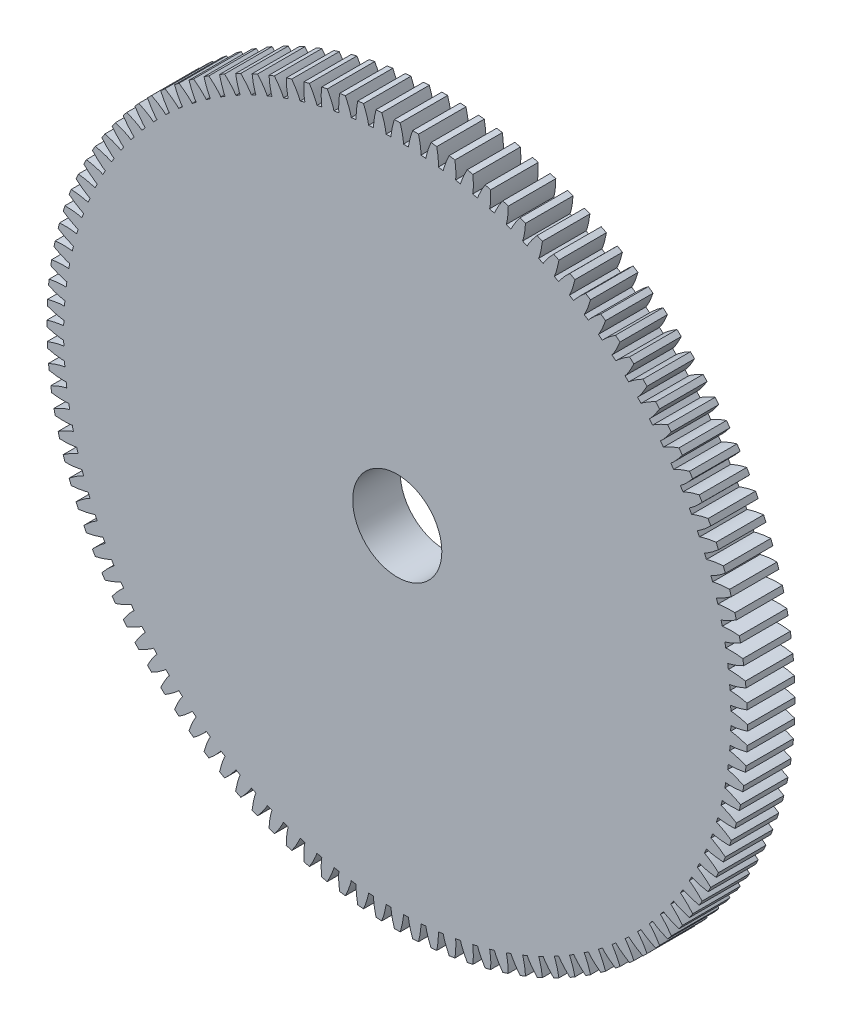
SolidWorks part; units mm, degrees
material "Brass"
ref_plane "Front Plane" through (0, 0, 0) normal (0, 0, 1) x (1, 0, 0)
ref_plane "Top Plane" through (0, 0, 0) normal (0, 1, 0) x (1, 0, 0)
ref_plane "Right Plane" through (0, 0, 0) normal (1, 0, 0) x (0, 0, -1)
sketch "Sketch1" plane through (0, 0, 0) normal (0, 0, 1) x (1, 0, 0)
  circle A0 centre (0, 0) radius 51.6467
extrude "Boss-Extrude1" add sketch "Sketch1" along normal blind 7
sketch "Sketch2" plane through (0, 0, 0) normal (0, 0, 1) x (1, 0, 0)
  circle A0 centre (0, 0) radius 6.5714
  dimension "D1" = 13.1428
extrude "Cut-Extrude2" cut sketch "Sketch2" against normal blind 9 and the other way blind 9
sketch "Sketch3" plane through (0, 0, 0) normal (0, 0, 1) x (1, 0, 0)
  spline S0 degree 4 poles (49.1734, 0.9164) (49.1838, 0.9166) (49.2037, 0.9164) (49.236, 0.9157) (49.2811, 0.9138) (49.3345, 0.9109) (49.3975, 0.9065) (49.4669, 0.9007) (49.5426, 0.8933) (49.6181, 0.8849) (49.6937, 0.8757) (49.769, 0.8656) (49.8604, 0.8525) (49.9703, 0.8355) (50.099, 0.8136) (50.2454, 0.7864) (50.3952, 0.7562) (50.5429, 0.7245) (50.6927, 0.69) (50.8381, 0.655) (50.9896, 0.6161) (51.1298, 0.579) (51.2875, 0.5348) (51.415, 0.4982) (51.584, 0.4471) (51.6841, 0.416) (51.8014, 0.3786) (51.8537, 0.3614) (51.8859, 0.3509) knots 0 0 0 0 0 0.015084 0.028532 0.04661 0.064855 0.092111 0.119476 0.146842 0.174209 0.201575 0.228941 0.256307 0.307035 0.361767 0.4165 0.471232 0.525964 0.580697 0.635429 0.690161 0.744894 0.799626 0.854358 0.909091 0.954545 1 1 1 1 1 construction
  spline S1 degree 4 poles (49.1734, 0.9164) (49.1838, 0.9166) (49.2037, 0.9164) (49.236, 0.9157) (49.2811, 0.9138) (49.3345, 0.9109) (49.3975, 0.9065) (49.4669, 0.9007) (49.5426, 0.8933) (49.6181, 0.8849) (49.6937, 0.8757) (49.769, 0.8656) (49.8604, 0.8525) (49.9703, 0.8355) (50.099, 0.8136) (50.2454, 0.7864) (50.3952, 0.7562) (50.5429, 0.7245) (50.6927, 0.69) (50.8381, 0.655) (50.9896, 0.6161) (51.1298, 0.579) (51.2875, 0.5348) (51.415, 0.4982) (51.5474, 0.4582) (51.6119, 0.4383) (51.6449, 0.428) knots 0 0 0 0 0 0.015084 0.028532 0.04661 0.064855 0.092111 0.119476 0.146842 0.174209 0.201575 0.228941 0.256307 0.307035 0.361767 0.4165 0.471232 0.525964 0.580697 0.635429 0.690161 0.744894 0.799626 0.854358 0.909091 0.909091 0.909091 0.909091 0.909091
  spline S2 degree 4 poles (49.1539, 1.6583) (49.1644, 1.6588) (49.1842, 1.66) (49.2165, 1.6624) (49.2614, 1.6666) (49.3146, 1.6723) (49.3773, 1.68) (49.4463, 1.6894) (49.5214, 1.7008) (49.5965, 1.7131) (49.6714, 1.7263) (49.7461, 1.7403) (49.8367, 1.7581) (49.9455, 1.7809) (50.0729, 1.8095) (50.2177, 1.8443) (50.3657, 1.8823) (50.5116, 1.9217) (50.6594, 1.964) (50.8027, 2.0066) (50.952, 2.0533) (51.09, 2.0977) (51.2452, 2.1502) (51.3706, 2.1933) (51.5367, 2.2532) (51.635, 2.2895) (51.7503, 2.333) (51.8016, 2.3529) (51.8332, 2.3651) knots 0 0 0 0 0 0.015084 0.028532 0.04661 0.064855 0.092111 0.119476 0.146842 0.174209 0.201575 0.228941 0.256307 0.307035 0.361767 0.4165 0.471232 0.525964 0.580697 0.635429 0.690161 0.744894 0.799626 0.854358 0.909091 0.954545 1 1 1 1 1 construction
  spline S3 degree 4 poles (49.1539, 1.6583) (49.1644, 1.6588) (49.1842, 1.66) (49.2165, 1.6624) (49.2614, 1.6666) (49.3146, 1.6723) (49.3773, 1.68) (49.4463, 1.6894) (49.5214, 1.7008) (49.5965, 1.7131) (49.6714, 1.7263) (49.7461, 1.7403) (49.8367, 1.7581) (49.9455, 1.7809) (50.0729, 1.8095) (50.2177, 1.8443) (50.3657, 1.8823) (50.5116, 1.9217) (50.6594, 1.964) (50.8027, 2.0066) (50.952, 2.0533) (51.09, 2.0977) (51.2452, 2.1502) (51.3706, 2.1933) (51.5007, 2.2403) (51.5641, 2.2634) (51.5965, 2.2754) knots 0 0 0 0 0 0.015084 0.028532 0.04661 0.064855 0.092111 0.119476 0.146842 0.174209 0.201575 0.228941 0.256307 0.307035 0.361767 0.4165 0.471232 0.525964 0.580697 0.635429 0.690161 0.744894 0.799626 0.854358 0.909091 0.909091 0.909091 0.909091 0.909091
  spline S4 degree 4 poles (49.152, 1.7331) (49.1521, 1.7275) (49.1524, 1.7162) (49.1528, 1.7032) (49.1537, 1.6661) (49.1542, 1.6496) (49.1554, 1.6026) (49.1561, 1.5744) (49.1572, 1.5339) (49.158, 1.5022) (49.1589, 1.4673) (49.1598, 1.4358) (49.1606, 1.4032) (49.1615, 1.3704) (49.1623, 1.3377) (49.1632, 1.3038) (49.1641, 1.2685) (49.1651, 1.2321) (49.1661, 1.1947) (49.1671, 1.1572) (49.168, 1.1226) (49.1689, 1.0853) (49.1698, 1.0523) (49.1709, 1.0096) (49.1717, 0.9804) (49.1731, 0.927) (49.1735, 0.9094) (49.1745, 0.8714) (49.1749, 0.857) (49.1752, 0.847) (49.1753, 0.8418) knots 0 0 0 0 0 0.022088 0.044177 0.083333 0.119319 0.159813 0.201093 0.243304 0.280291 0.314751 0.350761 0.388774 0.424594 0.463227 0.497138 0.541352 0.583276 0.626202 0.666552 0.706902 0.743676 0.7856 0.828955 0.87417 0.916667 0.958835 0.979418 1 1 1 1 1 construction
  spline S5 degree 4 poles (49.1539, 1.6583) (49.1541, 1.6517) (49.1545, 1.6378) (49.1554, 1.6026) (49.1561, 1.5744) (49.1572, 1.5339) (49.158, 1.5022) (49.1589, 1.4673) (49.1598, 1.4358) (49.1606, 1.4032) (49.1615, 1.3704) (49.1623, 1.3377) (49.1632, 1.3038) (49.1641, 1.2685) (49.1651, 1.2321) (49.1661, 1.1947) (49.1671, 1.1572) (49.168, 1.1226) (49.1689, 1.0853) (49.1698, 1.0523) (49.1709, 1.0096) (49.1717, 0.9804) (49.1727, 0.94) (49.1732, 0.9243) (49.1734, 0.9164) knots 0.083333 0.083333 0.083333 0.083333 0.083333 0.119319 0.159813 0.201093 0.243304 0.280291 0.314751 0.350761 0.388774 0.424594 0.463227 0.497138 0.541352 0.583276 0.626202 0.666552 0.706902 0.743676 0.7856 0.828955 0.87417 0.916667 0.916667 0.916667 0.916667 0.916667
  spline S6 degree 4 poles (50.8043, 0.4211) (50.864, 0.4216) (50.9794, 0.4225) (51.1316, 0.4238) (51.5629, 0.4274) (51.7496, 0.4289) (52.3065, 0.4335) (52.6262, 0.4362) (53.0785, 0.4399) (53.4484, 0.443) (53.8676, 0.4465) (54.2464, 0.4496) (54.6546, 0.453) (55.0383, 0.4562) (55.4322, 0.4594) (55.8223, 0.4627) (56.2055, 0.4658) (56.6028, 0.4691) (56.9958, 0.4724) (57.4001, 0.4757) (57.7912, 0.479) (58.2102, 0.4825) (58.5784, 0.4855) (59.0365, 0.4893) (59.3484, 0.4919) (59.8904, 0.4964) (60.0774, 0.4979) (60.499, 0.5014) (60.6501, 0.5027) (60.7751, 0.5037) (60.8382, 0.5042) knots 0 0 0 0 0 0.020582 0.041165 0.083333 0.123922 0.164487 0.203919 0.245641 0.283463 0.324863 0.363448 0.401438 0.443624 0.479586 0.519794 0.557378 0.596758 0.637386 0.678142 0.716036 0.757316 0.79719 0.837516 0.878097 0.916667 0.955572 0.977786 1 1 1 1 1 construction
  spline S7 degree 4 poles (51.6449, 0.428) (51.7297, 0.4287) (51.8939, 0.4301) (52.3065, 0.4335) (52.6262, 0.4362) (53.0785, 0.4399) (53.4484, 0.443) (53.8676, 0.4465) (54.2464, 0.4496) (54.6546, 0.453) (55.0383, 0.4562) (55.4322, 0.4594) (55.8223, 0.4627) (56.2055, 0.4658) (56.6028, 0.4691) (56.9958, 0.4724) (57.4001, 0.4757) (57.7912, 0.479) (58.2102, 0.4825) (58.5784, 0.4855) (59.0365, 0.4893) (59.3484, 0.4919) (59.7573, 0.4953) (59.9173, 0.4966) (59.9978, 0.4973) knots 0.083333 0.083333 0.083333 0.083333 0.083333 0.123922 0.164487 0.203919 0.245641 0.283463 0.324863 0.363448 0.401438 0.443624 0.479586 0.519794 0.557378 0.596758 0.637386 0.678142 0.716036 0.757316 0.79719 0.837516 0.878097 0.916667 0.916667 0.916667 0.916667 0.916667
  spline S8 degree 4 poles (59.9992, 0.2811) (59.9991, 0.2966) (59.999, 0.3264) (59.9988, 0.3667) (59.998, 0.4759) (59.9976, 0.5237) (59.9963, 0.6646) (59.9953, 0.7445) (59.9938, 0.8601) (59.9923, 0.9543) (59.9905, 1.0614) (59.9887, 1.1607) (59.9866, 1.2646) (59.9844, 1.3658) (59.9819, 1.4686) (59.9794, 1.5706) (59.9766, 1.6727) (59.9736, 1.7754) (59.9706, 1.8766) (59.9672, 1.9805) (59.9639, 2.0797) (59.96, 2.1868) (59.9566, 2.2809) (59.952, 2.3964) (59.9488, 2.4763) (59.9428, 2.617) (59.9407, 2.6648) (59.9358, 2.7739) (59.9338, 2.8142) (59.9324, 2.844) (59.9317, 2.8594) knots 0 0 0 0 0 0.020959 0.041918 0.083333 0.123016 0.162698 0.202381 0.242063 0.281746 0.321429 0.361111 0.400794 0.440476 0.480159 0.519841 0.559524 0.599206 0.638889 0.678571 0.718254 0.757937 0.797619 0.837302 0.876984 0.916667 0.958082 0.979041 1 1 1 1 1 construction
  spline S9 degree 4 poles (59.9978, 0.4973) (59.9976, 0.5186) (59.9973, 0.5601) (59.9963, 0.6646) (59.9953, 0.7445) (59.9938, 0.8601) (59.9923, 0.9543) (59.9905, 1.0614) (59.9887, 1.1607) (59.9866, 1.2646) (59.9844, 1.3658) (59.9819, 1.4686) (59.9794, 1.5706) (59.9766, 1.6727) (59.9736, 1.7754) (59.9706, 1.8766) (59.9672, 1.9805) (59.9639, 2.0797) (59.96, 2.1868) (59.9566, 2.2809) (59.952, 2.3964) (59.9488, 2.4763) (59.9444, 2.5807) (59.9426, 2.6222) (59.9416, 2.6434) knots 0.083333 0.083333 0.083333 0.083333 0.083333 0.123016 0.162698 0.202381 0.242063 0.281746 0.321429 0.361111 0.400794 0.440476 0.480159 0.519841 0.559524 0.599206 0.638889 0.678571 0.718254 0.757937 0.797619 0.837302 0.876984 0.916667 0.916667 0.916667 0.916667 0.916667
  spline S10 degree 4 poles (60.7813, 2.6805) (60.7233, 2.6779) (60.6112, 2.673) (60.4593, 2.6663) (60.0264, 2.6472) (59.8505, 2.6394) (59.3125, 2.6157) (59.0208, 2.6028) (58.6061, 2.5846) (58.2603, 2.5693) (57.8595, 2.5516) (57.496, 2.5356) (57.0992, 2.5181) (56.7297, 2.5018) (56.3678, 2.4858) (56.0013, 2.4697) (55.6349, 2.4535) (55.2589, 2.4369) (54.8708, 2.4198) (54.4874, 2.4029) (54.084, 2.3851) (53.7043, 2.3684) (53.2954, 2.3503) (52.937, 2.3345) (52.5215, 2.3162) (52.2196, 2.3029) (51.696, 2.2798) (51.481, 2.2703) (51.015, 2.2498) (50.8906, 2.2443) (50.7566, 2.2384) knots 0 0 0 0 0 0.02008 0.040161 0.083333 0.123261 0.159319 0.197812 0.233027 0.26907 0.309878 0.349805 0.383268 0.424652 0.459253 0.493239 0.530412 0.57034 0.610222 0.64719 0.685114 0.729048 0.765971 0.80369 0.838967 0.877741 0.916667 0.958333 1 1 1 1 1 construction
  spline S11 degree 4 poles (59.9416, 2.6434) (59.8583, 2.6398) (59.7031, 2.6329) (59.3125, 2.6157) (59.0208, 2.6028) (58.6061, 2.5846) (58.2603, 2.5693) (57.8595, 2.5516) (57.496, 2.5356) (57.0992, 2.5181) (56.7297, 2.5018) (56.3678, 2.4858) (56.0013, 2.4697) (55.6349, 2.4535) (55.2589, 2.4369) (54.8708, 2.4198) (54.4874, 2.4029) (54.084, 2.3851) (53.7043, 2.3684) (53.2954, 2.3503) (52.937, 2.3345) (52.5215, 2.3162) (52.2196, 2.3029) (51.8371, 2.286) (51.6777, 2.279) (51.5965, 2.2754) knots 0.083333 0.083333 0.083333 0.083333 0.083333 0.123261 0.159319 0.197812 0.233027 0.26907 0.309878 0.349805 0.383268 0.424652 0.459253 0.493239 0.530412 0.57034 0.610222 0.64719 0.685114 0.729048 0.765971 0.80369 0.838967 0.877741 0.916667 0.916667 0.916667 0.916667 0.916667
extrude "Cut-Extrude4" cut sketch "Sketch3" against normal blind 8 and the other way blind 8
ref_axis "Axis1" through (0, 0, -0.35) along (0, 0, 1)
pattern_circular "CirPattern1" count 120 over 360 about axis through (0, 0, -0.35) along (0, 0, 1) of "Cut-Extrude4"
equation "\"TrigProbe\"= cos(60)"
equation "\"SqrProbe\"= sqr(2)"
equation "\"AtnProbe\"= atn(1)"
equation "\"ToothCount\" = 120"
equation "\"DP\"= 30"
equation "\"PA\"= 14.5"
equation "\"PArad\"= \"PA\" * 3.14159265358979 / 180"
equation "\"Rb\"= \"ToothCount\" / \"DP\" * cos(\"PA\") / 2"
equation "\"Ra\"= (\"ToothCount\" + 2) / \"DP\" / 2"
equation "\"Tmax\"= sqr(\"Ra\" * \"Ra\" / (\"Rb\" * \"Rb\") - 1)"
equation "\"Delta\"= 3.14159265358979 / (2 * \"ToothCount\") + tan(\"PA\") - \"PArad\""
equation "\"Gamma\"= 2 * 3.14159265358979 / \"ToothCount\""
equation "\"ThetaL\"= atn(\"Tmax\") * 3.14159265358979 / 180 - \"Tmax\" + \"Delta\""
equation "\"ThetaU\"= \"Tmax\" - atn(\"Tmax\") * 3.14159265358979 / 180 - \"Delta\" + \"Gamma\""
equation "\"D1@Sketch1\" = 2 * \"Ra\""
equation "\"BoreDia\" = 0.517432"
equation "\"D1@Sketch2\" = \"BoreDia\""
equation "\"D1@CirPattern1\" = \"ToothCount\""
